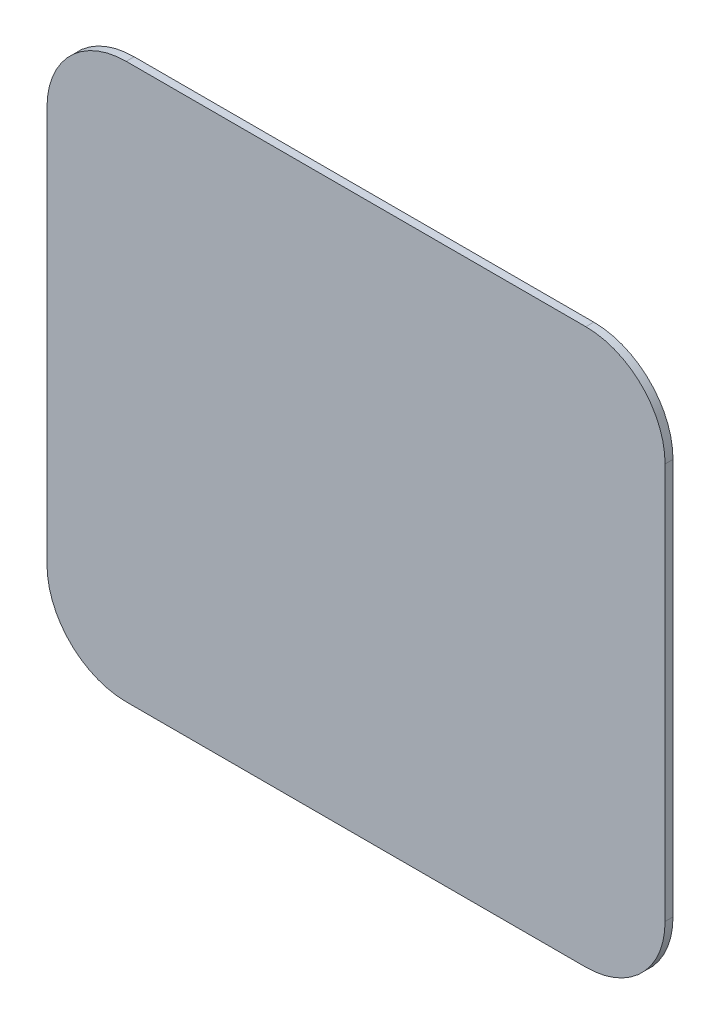
SolidWorks part; units mm, degrees
ref_plane "Front Plane" through (0, 0, 0) normal (0, 0, 1) x (1, 0, 0)
ref_plane "Top Plane" through (0, 0, 0) normal (0, 1, 0) x (1, 0, 0)
ref_plane "Right Plane" through (0, 0, 0) normal (1, 0, 0) x (0, 0, -1)
sketch "Sketch1" plane through (0, 0, 0) normal (0, 0, 1) x (1, 0, 0)
  line L0 (85.3333, 256) -> (81.5286, 231.264) construction
  line L1 (-153.9588, 7.6106) -> (187.3745, 7.6106) construction
  line L7 (-39.0754, 39.9502) -> (38.9246, 39.9502)
  line L8 (-39.0754, 39.9502) -> (-39.0754, -30.0498)
  line L9 (-39.0754, -30.0498) -> (38.9246, -30.0498)
  line L10 (38.9246, 39.9502) -> (38.9246, -30.0498)
  point P0 (0, 0)
  point P6 (0, 0)
  dimension "D1" = 78
  dimension "D2" = 70
extrude "Boss-Extrude1" add sketch "Sketch1" along normal blind 1
fillet "Fillet1" radius 10 4 edges at (-39.0754, 39.9502, 0.5) (-39.0754, -30.0498, 0.5) (38.9246, -30.0498, 0.5) (38.9246, 39.9502, 0.5)
sketch "Sketch2" plane through (0, 0, 0) normal (0, 0, -1) x (-1, 0, 0)
  line L0 (-28.9246, 39.9502) -> (29.0754, 39.9502) construction
  line L1 (29.0754, -30.0498) -> (-28.9246, -30.0498) construction
  line L2 (39.0754, 29.9502) -> (39.0754, -20.0498) construction
  line L3 (-38.9246, -20.0498) -> (-38.9246, 29.9502) construction
  line L4 (0.0754, 4.9502) -> (32.5754, -27.5498) construction
  line L5 (0.0754, 4.9502) -> (32.5754, 37.4502) construction
  line L6 (0.0754, 4.9502) -> (-32.4246, 37.4502) construction
  line L7 (0.0754, 4.9502) -> (-32.4246, -27.5498) construction
  line L8 (32.5754, 37.4502) -> (32.5754, -27.5498) construction
  line L9 (32.5754, -27.5498) -> (-32.4246, -27.5498) construction
  line L10 (-32.4246, -27.5498) -> (-32.4246, 37.4502) construction
  line L11 (-32.4246, 37.4502) -> (32.5754, 37.4502) construction
  line L12 (-21.1378, 26.1634) -> (-17.6023, 22.6279)
  line L13 (-21.1378, -16.263) -> (-17.6023, -12.7275)
  line L14 (21.2886, 26.1634) -> (17.7531, 22.6279)
  line L15 (12.4498, 17.3246) -> (8.9142, 13.789)
  line L16 (8.9142, 13.789) -> (8.9228, 13.8599)
  line L17 (21.2886, -16.263) -> (17.7531, -12.7275)
  line L18 (12.4498, -7.4242) -> (8.9142, -3.8886)
  line L19 (0.0754, 4.9502) -> (0.0754, 39.9502) construction
  line L20 (0.0754, 39.9502) -> (0.0754, -30.0498) construction
  line L21 (-12.299, 17.3246) -> (-8.7634, 13.789)
  line L22 (-12.299, -7.4242) -> (-8.7634, -3.8886)
  circle A0 centre (0.0754, 4.9502) radius 5
  arc A1 (8.9142, -3.8886) -> (8.9142, 13.789) centre (0.0754, 4.9502) ccw
  arc A2 (12.4498, -7.4242) -> (12.4498, 17.3246) centre (0.0754, 4.9502) ccw
  arc A3 (17.7531, -12.7275) -> (17.7531, 22.6279) centre (0.0754, 4.9502) ccw
  arc A4 (21.2886, -16.263) -> (21.2886, 26.1634) centre (0.0754, 4.9502) ccw
  arc A5 (-21.1378, -16.263) -> (-21.1378, 26.1634) centre (0.0754, 4.9502) cw
  arc A6 (-17.6023, -12.7275) -> (-17.6023, 22.6279) centre (0.0754, 4.9502) cw
  arc A7 (-12.299, -7.4242) -> (-12.299, 17.3246) centre (0.0754, 4.9502) cw
  arc A8 (-8.7634, -3.8886) -> (-8.7634, 13.789) centre (0.0754, 4.9502) cw
  point P26 (12.5754, 4.9502)
  point P27 (17.5754, 4.9502)
  point P28 (25.0754, 4.9502)
  point P29 (30.0754, 4.9502)
  dimension "D15" = 10
  dimension "D17" = 17.5
  dimension "D1" = 35
  dimension "D2" = 39
  dimension "D3" = 35
  dimension "D4" = 39
  dimension "D5" = 90
  dimension "D6" = 90
  dimension "D7" = 90
  dimension "D8" = 90
  dimension "D9" = 90
  dimension "D10" = 90
  dimension "D11" = 90
  dimension "D12" = 90
  dimension "D13" = 65
  dimension "D14" = 65
  dimension "D16" = 12.5
  dimension "D18" = 25
  dimension "D19" = 30
extrude "Cut-Extrude1" cut sketch "Sketch2" against normal blind 0.1 contours L17 A4 L14 A3 | L18 A2 L15 A1 | A0 | L22 A8 L21 A7 | L13 A6 L12 A5 region at (19.6824, 24.0832, 0) region at (-29.6336, 4.9502, 0) region at (-13.7052, 4.9502, 0) region at (13.5544, 4.9502, 0) region at (-0.0754, 4.9502, 0)
